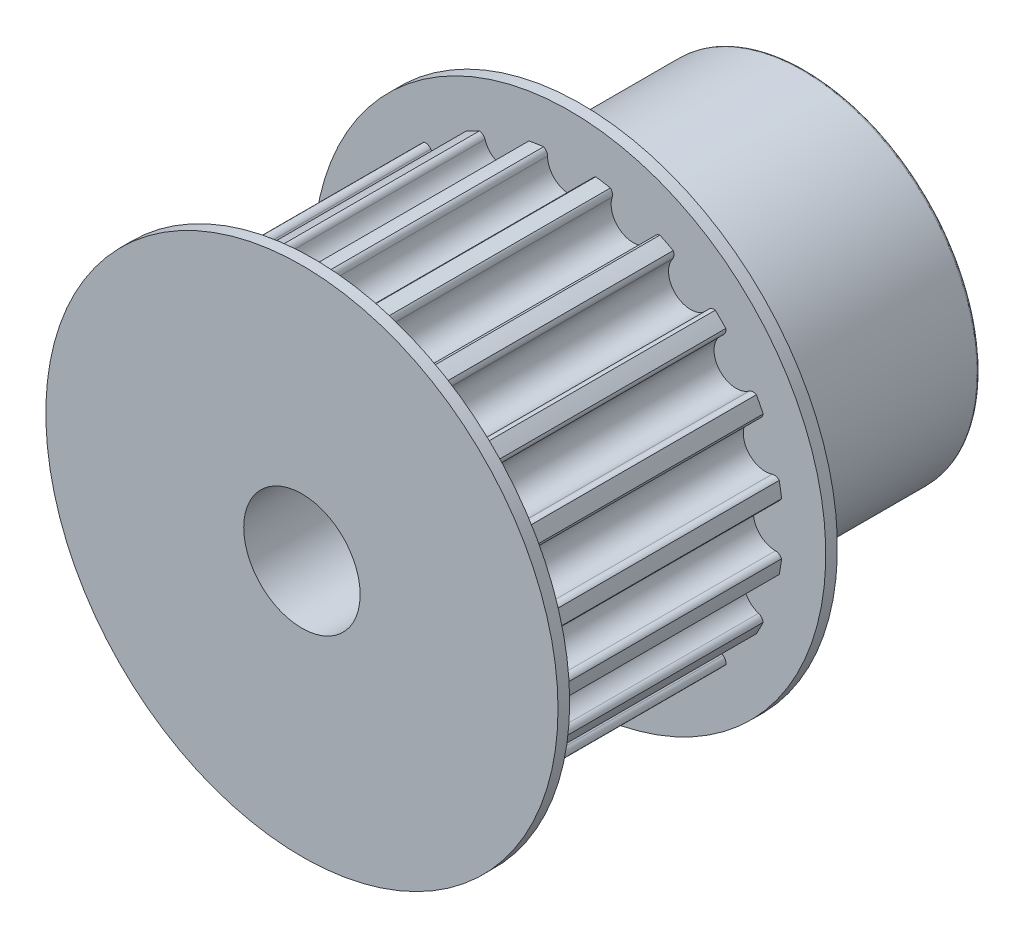
SolidWorks part; units mm, degrees
ref_plane "前基準面" through (0, 0, 0) normal (0, 0, 1) x (1, 0, 0)
ref_plane "上基準面" through (0, 0, 0) normal (0, 1, 0) x (1, 0, 0)
ref_plane "右基準面" through (0, 0, 0) normal (1, 0, 0) x (0, 0, -1)
sketch "草圖1" plane through (0, 0, 0) normal (0, 0, 1) x (1, 0, 0)
  circle A0 centre (0, 0) radius 9.17
  dimension "D1" = 18.34
extrude "填料-伸長1" add sketch "草圖1" along normal blind 11
sketch "草圖2" plane through (0, 0, 11) normal (0, 0, 1) x (1, 0, 0)
  line L0 (-1.1175, 9.1016) -> (0, 0) construction
  line L1 (0, 0) -> (1.1175, 9.1016) construction
  arc A0 (-1.1175, 9.1016) -> (1.1175, 9.1016) centre (0, 0) cw
  circle A1 centre (0, 0) radius 9.17 construction
  arc A2 (-1.1175, 9.1016) -> (-0.95, 8.84) centre (-1.2499, 8.8324) cw
  arc A3 (1.1175, 9.1016) -> (0.95, 8.84) centre (1.2499, 8.8324) ccw
  arc A4 (-0.95, 8.84) -> (0.95, 8.84) centre (0, 8.84) ccw
  point P12 (0, 9.17)
  point P13 (0, 7.89)
  dimension "D2" = 1.28
  dimension "D3" = 0.3
  dimension "D4" = 0.3
  dimension "D5" = 14
  dimension "D1" = 1.9
extrude "除料-伸長1" cut sketch "草圖2" against normal up to next
pattern_circular "環狀複製排列1" count 20 over 360 about axis through (0, 0, 11) along (0, 0, 1) of "除料-伸長1"
sketch "草圖3" plane through (0, 0, 11) normal (0, 0, 1) x (1, 0, 0)
  circle A0 centre (0, 0) radius 11
  dimension "D1" = 22
extrude "填料-伸長2" add sketch "草圖3" along normal blind 0.5
sketch "草圖4" plane through (0, 0, 0) normal (0, 0, -1) x (-1, 0, 0)
  circle A0 centre (0, 0) radius 11
  dimension "D1" = 22
extrude "填料-伸長3" add sketch "草圖4" along normal blind 0.5
sketch "草圖5" plane through (0, 0, -0.5) normal (0, 0, -1) x (-1, 0, 0)
  circle A0 centre (0, 0) radius 7.5
  dimension "D1" = 15
extrude "填料-伸長4" add sketch "草圖5" along normal blind 10
sketch "草圖6" plane through (0, 0, -10.5) normal (0, 0, -1) x (-1, 0, 0)
  circle A0 centre (0, 0) radius 2.5
  dimension "D1" = 5
extrude "除料-伸長2" cut sketch "草圖6" against normal up to next
fillet "圓角1" radius 0.5 1 edges at (-7.5, 0, -10.5) second distance 3 first distance on face at (-7.5, 0, -10.5)
